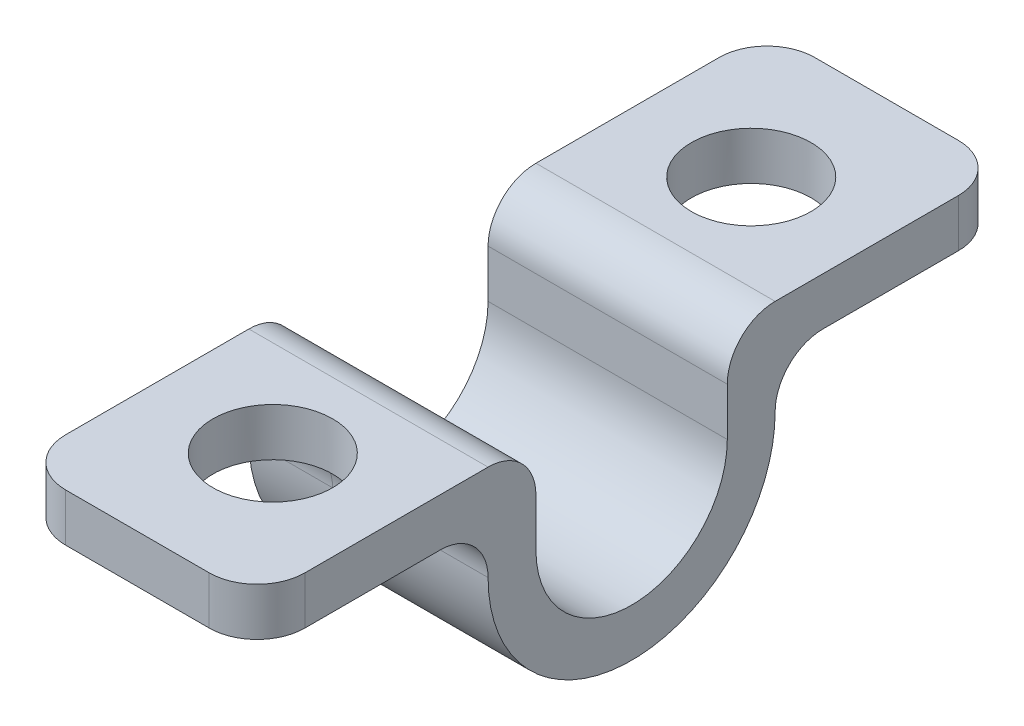
SolidWorks part; units mm, degrees
ref_plane "Front Plane" through (0, 0, 0) normal (0, 0, 1) x (1, 0, 0)
ref_plane "Top Plane" through (0, 0, 0) normal (0, 1, 0) x (1, 0, 0)
ref_plane "Right Plane" through (0, 0, 0) normal (1, 0, 0) x (0, 0, -1)
sketch "Sketch1" plane through (0, 0, 0) normal (1, 0, 0) x (0, 0, -1)
  line L0 (0, -1000) -> (0, 49000) construction
  line L1 (-1000, 0) -> (-4, 0) construction
  line L2 (-1000, -2) -> (49000, -2) construction
  line L9 (5.6569, -2) -> (15.6569, -2)
  line L10 (15.6569, -2) -> (15.6569, 0)
  line L11 (15.6569, 0) -> (4, 0)
  line L12 (-15.6569, -2) -> (-15.6569, 0)
  line L13 (-5.6569, -2) -> (-15.6569, -2)
  line L14 (4, -1000) -> (4, 49000) construction
  line L15 (-4, -1000) -> (-4, 49000) construction
  line L16 (4, 0) -> (49000, 0) construction
  line L17 (-1000, 0) -> (49000, 0) construction
  line L18 (-4, 0) -> (-15.6569, 0)
  line L19 (4, -4) -> (4, 0)
  line L20 (-4, -4) -> (-4, 0)
  arc A4 (-4, -4) -> (4, -4) centre (0, -4) ccw
  arc A5 (-5.6569, -2) -> (5.6569, -2) centre (0, -4) ccw
  point P15 (0, 0)
  dimension "D1" = 2
  dimension "D2" = 8
  dimension "D3" = 12
  dimension "D4" = 10
extrude "Boss-Extrude1" add sketch "Sketch1" along normal blind 10
sketch "Sketch3" plane through (0, 0, 0) normal (0, 1, 0) x (1, 0, 0)
  line L0 (-1000, 0) -> (49000, 0) construction
  line L1 (5, -984.3431) -> (5, 49015.6569) construction
  line L2 (10, 15.6569) -> (0, 15.6569) construction
  circle A0 centre (5, 10) radius 2.5
  circle A1 centre (5, -10) radius 2.5
  point P8 (5, 15.6569)
  dimension "D1" = 5
  dimension "D2" = 10
extrude "Cut-Extrude2" cut sketch "Sketch3" against normal up to next
fillet "Fillet2" radius 2 8 edges at (0, -1, -15.6569) (10, -1, -15.6569) (0, -1, 15.6569) (10, -1, 15.6569) (5, -2, 5.6569) (5, -2, -5.6569) (5, 0, -4) (5, 0, 4)
